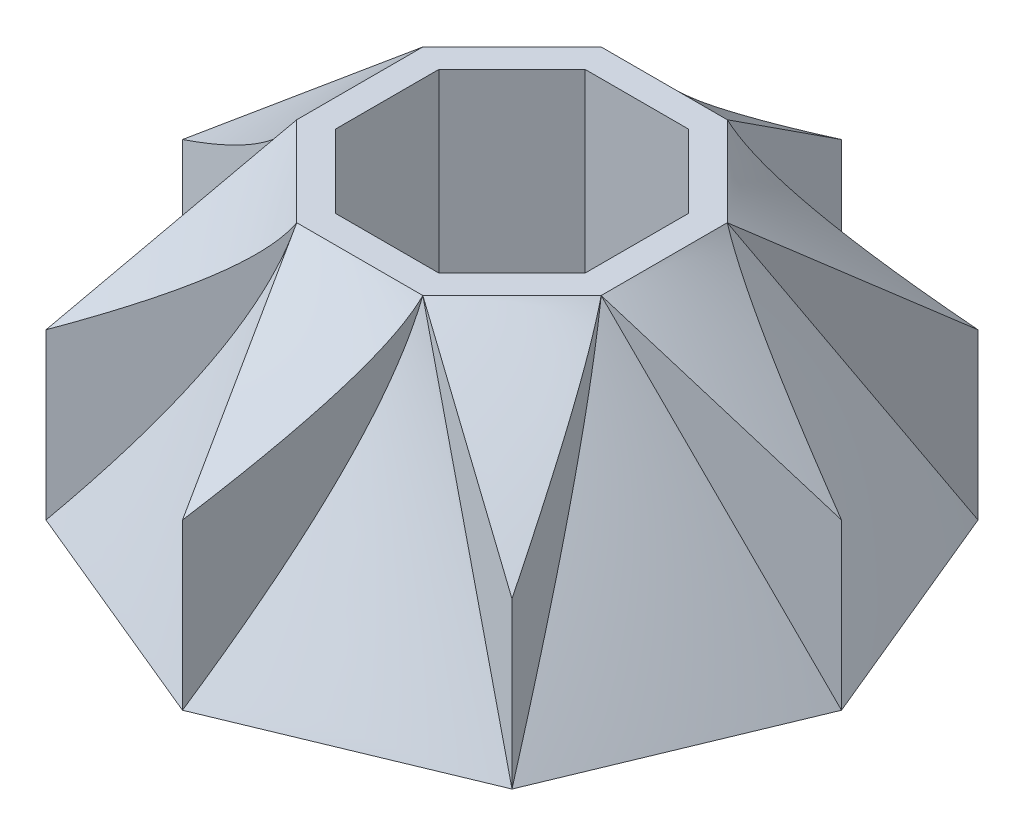
SolidWorks part; units mm, degrees
ref_plane "前视基准面" through (0, 0, 0) normal (0, 0, 1) x (1, 0, 0)
ref_plane "上视基准面" through (0, 0, 0) normal (0, 1, 0) x (1, 0, 0)
ref_plane "右视基准面" through (0, 0, 0) normal (1, 0, 0) x (0, 0, -1)
sketch "草图1" plane through (0, 0, 0) normal (0, 1, 0) x (1, 0, 0)
  line L1 (60, 0) -> (42.4264, 42.4264)
  line L2 (42.4264, 42.4264) -> (0, 60)
  line L3 (0, 60) -> (-42.4264, 42.4264)
  line L4 (-42.4264, 42.4264) -> (-60, 0)
  line L5 (-60, 0) -> (-42.4264, -42.4264)
  line L6 (-42.4264, -42.4264) -> (0, -60)
  line L7 (0, -60) -> (42.4264, -42.4264)
  line L8 (42.4264, -42.4264) -> (60, 0)
  circle A0 centre (0, 0) radius 55.4328 construction
  dimension "D1" = 120
ref_plane "基准面1" through (0, 55, 0) normal (0, 1, 0) x (1, 0, 0)
sketch "草图2" plane through (0, 55, 0) normal (0, 1, 0) x (1, 0, 0)
  line L0 (0, 0) -> (60, 0) construction
  line L1 (11.4805, 27.7164) -> (-11.4805, 27.7164)
  line L2 (-11.4805, 27.7164) -> (-27.7164, 11.4805)
  line L3 (-27.7164, 11.4805) -> (-27.7164, -11.4805)
  line L4 (-27.7164, -11.4805) -> (-11.4805, -27.7164)
  line L5 (-11.4805, -27.7164) -> (11.4805, -27.7164)
  line L6 (11.4805, -27.7164) -> (27.7164, -11.4805)
  line L7 (27.7164, -11.4805) -> (27.7164, 11.4805)
  line L8 (27.7164, 11.4805) -> (11.4805, 27.7164)
  line L9 (0, 0) -> (11.4805, 27.7164) construction
  circle A0 centre (0, 0) radius 27.7164 construction
  dimension "D1" = 67.5
  dimension "D2" = 60
sketch "草图6" plane through (0, 30, 0) normal (0, 1, 0) x (1, 0, 0)
  line L1 (-42.4264, 42.4264) -> (-60, 0)
  line L2 (-60, 0) -> (-42.4264, -42.4264)
  line L3 (-42.4264, -42.4264) -> (0, -60)
  line L4 (0, -60) -> (42.4264, -42.4264)
  line L5 (42.4264, -42.4264) -> (60, 0)
  line L6 (60, 0) -> (42.4264, 42.4264)
  line L7 (42.4264, 42.4264) -> (0, 60)
  line L8 (0, 60) -> (-42.4264, 42.4264)
  circle A0 centre (0, 0) radius 55.4328 construction
loft "放样7" add profiles "草图6<3>", "草图2" connector at (42.4264, 30, 42.4264) connector at (11.4805, 55, 27.7164)
sketch "草图6<3>" plane through (0, 30, 0) normal (0, 1, 0) x (1, 0, 0) same geometry as "草图6"
ref_plane "基准面2" through (0, 30, 0) normal (0, 1, 0) x (1, 0, 0)
extrude "凸台-拉伸1" add sketch "草图6" against normal blind 30
sketch "草图8" plane through (0, 55, 0) normal (0, 1, 0) x (1, 0, 0)
  line L4 (-42.4264, -42.4264) -> (-11.4805, -27.7164)
  line L5 (-42.4264, -42.4264) -> (0, -60) construction
  line L6 (0, -60) -> (-11.4805, -27.7164) construction
  line L7 (-42.4264, -42.4264) -> (0, -60)
  line L8 (0, -60) -> (-11.4805, -27.7164)
extrude "切除-拉伸3" cut sketch "草图8" against normal through all contours L8 L4 L7
sketch "草图9" plane through (0, 0, 0) normal (0, 0, 1) x (1, 0, 0)
  line L0 (0, 7.5213) -> (0, 63.0304)
  line L1 (0, -30.2501) -> (0, 30.2501) construction
  point P6 (0, 35.2758)
pattern_circular "阵列(圆周)2" count 8 over 360 about axis through (0, 7.5213, 0) along (0, 1, 0) of "切除-拉伸3" reverse direction yes
loft "放样8" add profiles "草图1", "草图2<47>" connector at (0, 0, 60) connector at (-11.4805, 55, 27.7164)
sketch "草图2<47>" plane through (0, 55, 0) normal (0, 1, 0) x (1, 0, 0) same geometry as "草图2"
sketch "草图10" plane through (0, 55, 0) normal (0, 1, 0) x (1, 0, 0)
  line L0 (11.4805, 27.7164) -> (-11.4805, 27.7164) construction
  line L1 (9.4094, 22.7164) -> (-9.4094, 22.7164)
  line L2 (-9.4094, 22.7164) -> (-22.7164, 9.4094)
  line L3 (-22.7164, 9.4094) -> (-22.7164, -9.4094)
  line L4 (-22.7164, -9.4094) -> (-9.4094, -22.7164)
  line L5 (-9.4094, -22.7164) -> (9.4094, -22.7164)
  line L6 (9.4094, -22.7164) -> (22.7164, -9.4094)
  line L7 (22.7164, -9.4094) -> (22.7164, 9.4094)
  line L8 (22.7164, 9.4094) -> (9.4094, 22.7164)
  circle A0 centre (0, 0) radius 22.7164 construction
  dimension "D1" = 5
extrude "切除-拉伸4" cut sketch "草图10" against normal through all
